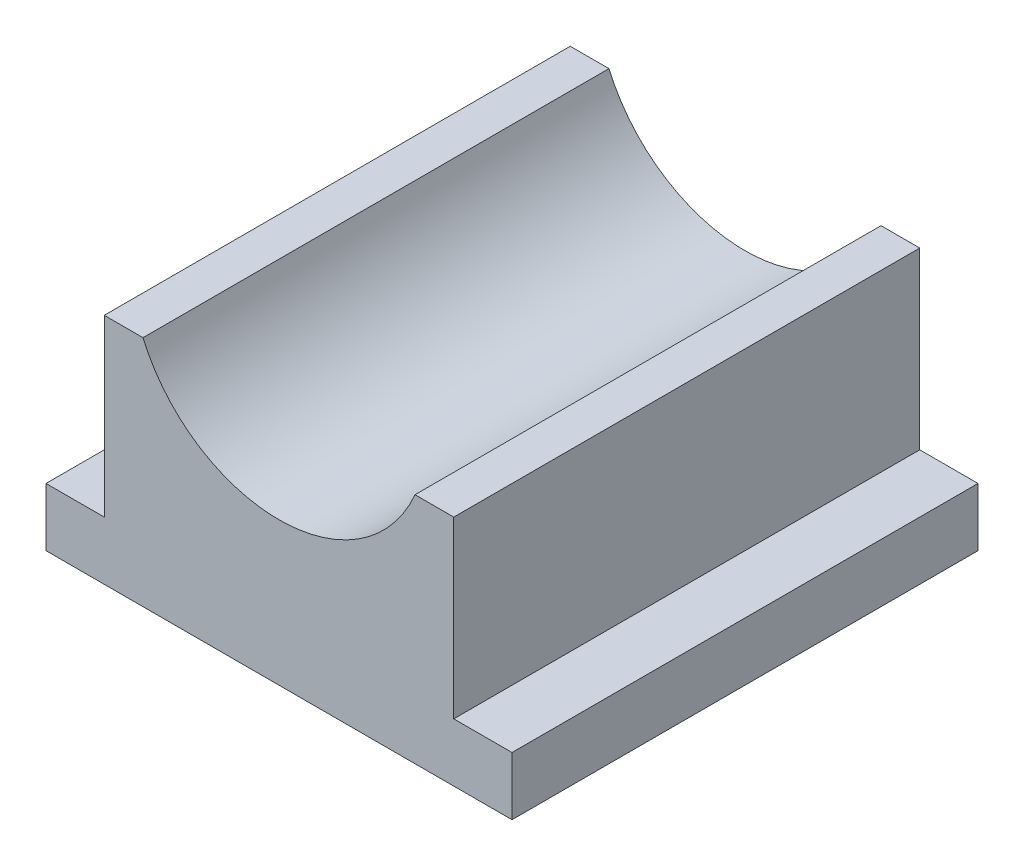
SolidWorks part; units mm, degrees
ref_plane "XY" through (0, 0, 0) normal (0, 0, 1) x (1, 0, 0)
ref_plane "XZ" through (0, 0, 0) normal (0, 1, 0) x (1, 0, 0)
ref_plane "YZ" through (0, 0, 0) normal (1, 0, 0) x (0, 0, -1)
ref_axis "X" through (-55.88, 0, 0) along (1, 0, 0)
ref_axis "Y" through (0, -66.04, 0) along (0, 1, 0)
ref_axis "Z" through (0, 0, 80.01) along (0, 0, -1)
sketch "Sketch1" plane through (0, 0, 0) normal (0, 0, 1) x (1, 0, 0)
  line L0 (-50.8, -63.5) -> (50.8, -63.5)
  line L1 (50.8, -63.5) -> (50.8, -50.8)
  line L2 (50.8, -50.8) -> (38.1, -50.8)
  line L5 (-38.1, -50.8) -> (-50.8, -50.8)
  line L6 (-50.8, -50.8) -> (-50.8, -63.5)
  line L7 (0, -32.258) -> (0, -63.5) construction
  line L8 (-29.6528, -12.7) -> (-38.1, -12.7)
  line L9 (-38.1, -12.7) -> (-38.1, -50.8)
  line L10 (29.6528, -12.7) -> (38.1, -12.7)
  line L11 (38.1, -12.7) -> (38.1, -50.8)
  arc A0 (29.6528, -12.7) -> (-29.6528, -12.7) centre (0, 0) cw
  point P7 (0, 0)
  point P14 (-44.58, -13.8607)
  dimension "D1" = 32.258
  dimension "D2" = 101.6
  dimension "D3" = 12.7
  dimension "D4" = 63.5
  dimension "D5" = 12.7
  dimension "D6" = 12.7
extrude "Boss-Extrude1" add sketch "Sketch1" along normal blind 101.6
